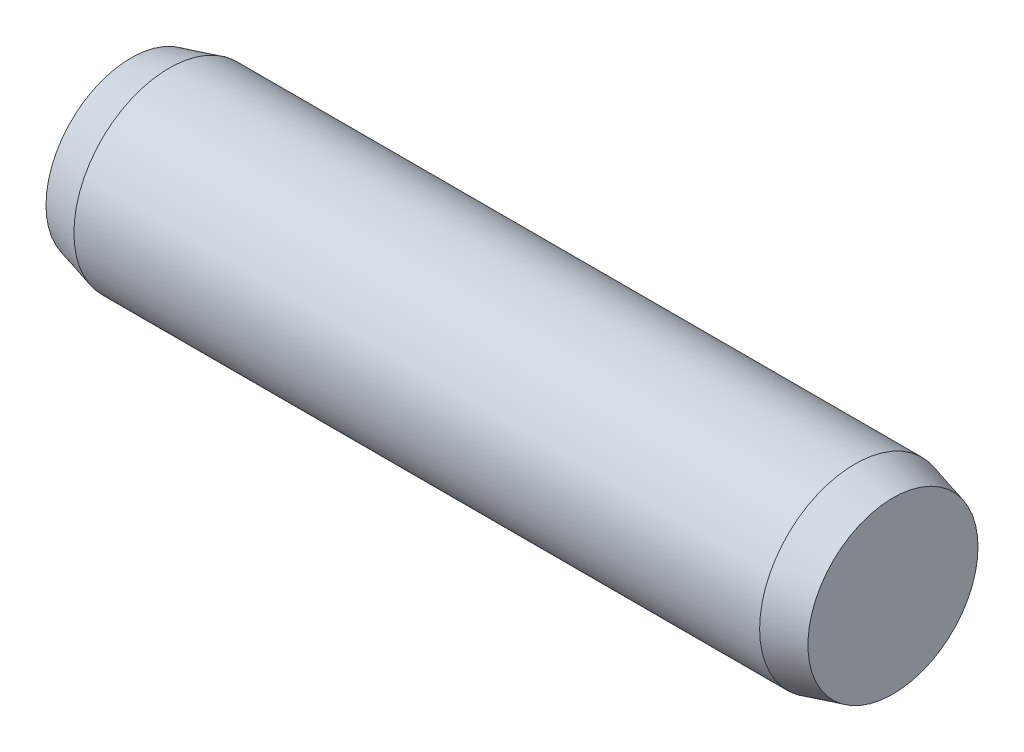
SolidWorks part; units mm, degrees
material "AISI 316 Stainless Steel Sheet (SS)"
ref_plane "Front Plane" through (0, 0, 0) normal (0, 0, 1) x (1, 0, 0)
ref_plane "Top Plane" through (0, 0, 0) normal (0, 1, 0) x (1, 0, 0)
ref_plane "Right Plane" through (0, 0, 0) normal (1, 0, 0) x (0, 0, -1)
sketch "Sketch1" plane through (0, 0, 0) normal (0, 0, 1) x (1, 0, 0)
  line L0 (-2.7, 0) -> (2.7, 0) construction
  line L1 (2.7, 0.75) -> (2.7, -0.75) construction
  line L2 (-2.7, 0.75) -> (-2.7, -0.75) construction
  line L3 (3, 0.75) -> (3, -0.75) construction
  line L4 (-3, 0.75) -> (-3, -0.75) construction
  line L5 (-2.7, 0) -> (-3, 0) construction
  line L6 (2.7, 0) -> (3, 0) construction
  dimension "Dia" = 1.5
  dimension "C" = 0.3
  dimension "D1" = 0.3
  dimension "Length" = 6
sketch "Sketch2" plane through (0, 0, 0) normal (1, 0, 0) x (0, 0, -1)
  circle A0 centre (0, 0) radius 0.75
extrude "Extrude1" add sketch "Sketch2" against normal up to vertex (2.7 mm away) and the other way up to vertex (2.7 mm away) up to point (-2.7, 0.75, 0) other way up to point (2.7, 0.75, 0)
sketch "Sketch3" plane through (2.7, 0, 0) normal (1, 0, 0) x (0, 0, -1)
  circle A1 centre (0, 0) radius 0.75
  circle A2 centre (0, 0) radius 0.75
  dimension "D1" = 0
extrude "Extrude2" add sketch "Sketch3" along normal up to vertex (0.3 mm away) draft 15 up to point (3, 0, 0)
sketch "Sketch4" plane through (-2.7, 0, 0) normal (-1, 0, 0) x (0, 0, 1)
  circle A1 centre (0, 0) radius 0.75
  circle A2 centre (0, 0) radius 0.75
  dimension "D1" = 0
extrude "Extrude3" add sketch "Sketch4" along normal up to vertex (0.3 mm away) draft 15 up to point (-3, 0, 0)
equation "\"D1@Sketch1\" = \"C@Sketch1\""
